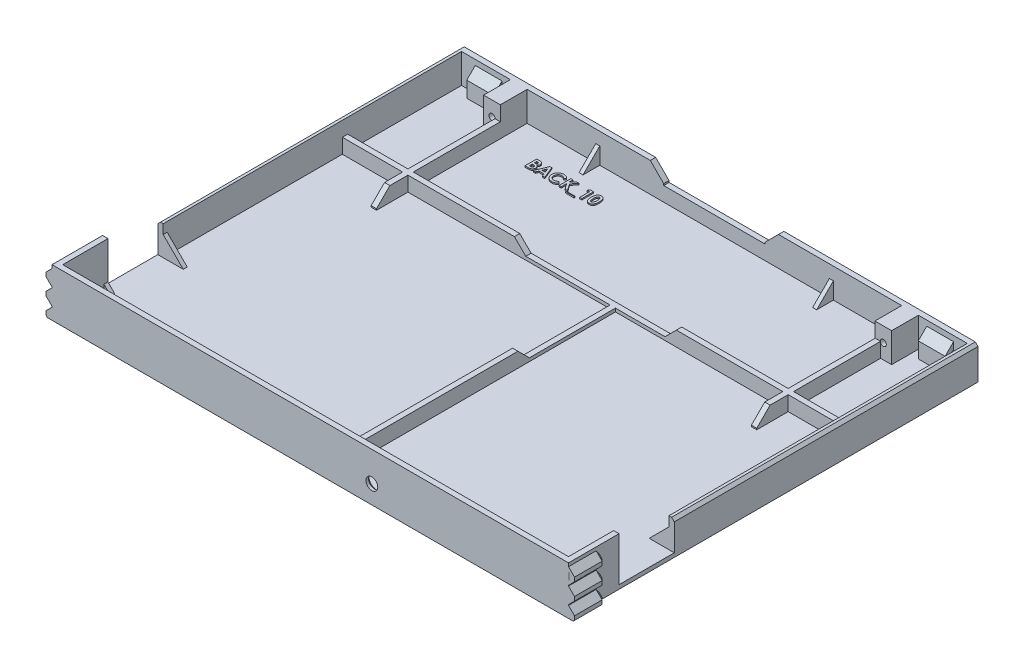
SolidWorks part; units mm, degrees
ref_plane "Front Plane" through (0, 0, 0) normal (0, 0, 1) x (1, 0, 0)
ref_plane "Top Plane" through (0, 0, 0) normal (0, 1, 0) x (1, 0, 0)
ref_plane "Right Plane" through (0, 0, 0) normal (1, 0, 0) x (0, 0, -1)
other "Version"
sketch "Sketch1" plane through (0, 0, 0) normal (0, 1, 0) x (1, 0, 0)
  line L3 (-77.15, -61.17) -> (77.15, -61.17)
  line L5 (-77.15, 61.17) -> (77.15, -61.17) construction
  line L6 (-77.15, -61.17) -> (77.15, 61.17) construction
  line L13 (-77.15, 61.17) -> (-77.15, -61.17)
  line L18 (77.15, 61.17) -> (-77.15, 61.17)
  line L20 (77.15, 61.17) -> (77.15, -61.17)
  point P0 (0, 0)
  point P6 (0, 0)
  dimension "D3" = 154.3
  dimension "D1" = 154.3
  dimension "D2" = 122.34
extrude "flat_on_wall" add sketch "Sketch1" along normal blind 1.2
sketch "Sketch3" plane through (0, 0, 0) normal (0, 1, 0) x (1, 0, 0)
  line L0 (-77.15, -29.57) -> (-77.15, 61.17)
  line L1 (-77.15, 61.17) -> (-77.15, -61.17) construction
  line L2 (-77.15, 61.17) -> (-45.55, 61.17)
  line L3 (77.15, 61.17) -> (-77.15, 61.17) construction
  line L6 (-75.55, 59.57) -> (-75.55, -29.57)
  line L7 (-75.55, -29.57) -> (-77.15, -29.57)
  line L8 (45.55, 61.17) -> (77.15, 61.17)
  line L9 (77.15, 61.17) -> (77.15, -29.57)
  line L10 (77.15, -61.17) -> (77.15, 61.17) construction
  line L11 (77.15, -29.57) -> (75.55, -29.57)
  line L12 (75.55, -29.57) -> (75.55, 59.57)
  line L15 (-77.15, -46.07) -> (-77.15, -61.17)
  line L16 (-77.15, -61.17) -> (77.15, -61.17)
  line L17 (77.15, -61.17) -> (77.15, -46.07)
  line L18 (77.15, -46.07) -> (75.55, -46.07)
  line L19 (75.55, -46.07) -> (75.55, -59.57)
  line L20 (75.55, -59.57) -> (-75.55, -59.57)
  line L21 (-75.55, -59.57) -> (-75.55, -46.07)
  line L22 (-75.55, -46.07) -> (-77.15, -46.07)
  line L23 (-75.55, 59.57) -> (-60.95, 59.57)
  line L24 (-60.95, 59.57) -> (-60.95, 51.57)
  line L25 (-60.95, 51.57) -> (-55.95, 51.57)
  line L26 (-55.95, 51.57) -> (-55.95, 59.57)
  line L27 (-55.95, 59.57) -> (-45.55, 59.57)
  line L28 (75.55, 59.57) -> (60.95, 59.57)
  line L29 (60.95, 59.57) -> (60.95, 51.57)
  line L30 (60.95, 51.57) -> (55.95, 51.57)
  line L31 (55.95, 51.57) -> (55.95, 59.57)
  line L32 (55.95, 59.57) -> (45.55, 59.57)
  line L34 (-45.55, 59.57) -> (45.55, 59.57)
  line L36 (-45.55, 61.17) -> (45.55, 61.17)
  point P25 (-76.35, -46.07)
  dimension "D2" = 1.6
  dimension "D3" = 30
  dimension "D4" = 16.5
  dimension "D5" = 5
  dimension "D6" = 1.6
  dimension "D7" = 30
  dimension "D8" = 16.5
  dimension "D9" = 1.6
  dimension "D10" = 13.5
  dimension "D11" = 1.6
  dimension "D12" = 1.6
  dimension "D13" = 13.5
  dimension "D14" = 14.6
  dimension "D15" = 5
  dimension "D16" = 8
  dimension "D17" = 8
  dimension "D18" = 8
  dimension "D19" = 8
  dimension "D20" = 1.6
  dimension "D21" = 14.6
  dimension "D22" = 1.6
  dimension "D23" = 1.6
extrude "walls" add sketch "Sketch3" along normal blind 10
sketch "Sketch5" plane through (0, 0, 0) normal (1, 0, 0) x (0, 0, -1)
  line L0 (-61.17, 10) -> (-61.17, 0) construction
  line L5 (-61.17, 0) -> (-51.97, 0)
  line L6 (-61.17, 0) -> (-61.17, 2)
  line L7 (-61.17, 2) -> (-51.97, 2)
  line L8 (-51.97, 0) -> (-51.97, 2)
  line L9 (-61.17, 0) -> (61.17, 0) construction
  line L10 (-61.17, 10) -> (-51.97, 10)
  line L11 (-61.17, 5) -> (-51.97, 5)
  line L12 (-61.17, 5) -> (-61.17, 7)
  line L13 (-61.17, 7) -> (-51.97, 7)
  line L14 (-51.97, 5) -> (-51.97, 7)
  line L15 (-61.17, 10) -> (-61.17, 12)
  line L16 (-61.17, 12) -> (-51.97, 12)
  line L17 (-51.97, 10) -> (-51.97, 12)
  line L18 (-61.17, 10) -> (-46.07, 10) construction
  dimension "D1" = 0
  dimension "D2" = 9.2
  dimension "D3" = 2
  dimension "D4" = 9.2
  dimension "D5" = 2
  dimension "D6" = 3
  dimension "D7" = 2
extrude "rails" add sketch "Sketch5" along normal blind 0.75 from surface starting at face at (77.15, 5.3, 18.91)
sketch "Sketch6" plane through (0, 0, 0) normal (1, 0, 0) x (0, 0, -1)
  line L0 (-61.17, 12) -> (-51.97, 12)
  line L1 (-61.17, 2) -> (-51.97, 2)
  line L2 (-61.17, 2) -> (-61.17, 0)
  line L3 (-61.17, 0) -> (-51.97, 0)
  line L4 (-51.97, 2) -> (-51.97, 0)
  line L5 (-61.17, 7) -> (-51.97, 7)
  line L6 (-61.17, 7) -> (-61.17, 5)
  line L7 (-61.17, 5) -> (-51.97, 5)
  line L8 (-51.97, 7) -> (-51.97, 5)
  line L9 (-61.17, 12) -> (-61.17, 10)
  line L10 (-61.17, 10) -> (-51.97, 10)
  line L11 (-51.97, 12) -> (-51.97, 10)
  dimension "D1" = 9.2
  dimension "D2" = 9.2
  dimension "D3" = 2
  dimension "D4" = 2
  dimension "D5" = 2
extrude "rails-left" add sketch "Sketch6" along normal blind 0.1 and the other way blind 1.8 from surface starting at face at (-77.15, 5.3, 18.91)
sketch "Sketch7" plane through (0, 0, 0) normal (0, 1, 0) x (1, 0, 0)
  line L0 (-47.15, 46.17) -> (-47.15, 39.9043) construction
  line L1 (-44.69, 46.17) -> (-44.69, 43.37)
  line L2 (-49.61, 46.17) -> (-49.61, 43.37)
  line L3 (77.15, 61.17) -> (-77.15, 61.17) construction
  line L4 (-77.15, -29.57) -> (-77.15, -46.07) construction
  line L5 (47.15, 46.17) -> (47.15, 39.9043) construction
  line L6 (49.61, 46.17) -> (49.61, 43.37)
  line L7 (44.69, 46.17) -> (44.69, 43.37)
  line L9 (77.15, -29.57) -> (77.15, 61.17) construction
  line L10 (77.15, 61.17) -> (-77.15, 61.17) construction
  line L13 (-77.05, -61.17) -> (77.15, -61.17) construction
  line L14 (-0.45, 8.83) -> (-0.45, 2.5643) construction
  line L15 (2.01, 8.83) -> (2.01, 6.03)
  line L16 (-2.91, 8.83) -> (-2.91, 6.03)
  line L17 (77.15, -46.07) -> (77.15, -29.57) construction
  arc A0 (-44.69, 46.17) -> (-49.61, 46.17) centre (-47.15, 46.17) ccw
  arc A3 (-44.69, 43.37) -> (-49.61, 43.37) centre (-47.15, 39.9043) cw
  arc A4 (49.61, 46.17) -> (44.69, 46.17) centre (47.15, 46.17) ccw
  arc A5 (49.61, 43.37) -> (44.69, 43.37) centre (47.15, 39.9043) cw
  arc A8 (2.01, 8.83) -> (-2.91, 8.83) centre (-0.45, 8.83) ccw
  arc A9 (2.01, 6.03) -> (-2.91, 6.03) centre (-0.45, 2.5643) cw
  point P2 (-47.9176, 44.8712)
  point P13 (43.1175, 41.9506)
  dimension "D1" = 15
  dimension "D5" = 2.46
  dimension "D9" = 4.25
  dimension "D2" = 30
  dimension "D3" = 15
  dimension "D4" = 30
  dimension "D6" = 6.2657
  dimension "D7" = 77.6
  dimension "D8" = 70
extrude "Cut-Extrude7" [suppressed] cut sketch "Sketch7" against normal through all from surface
sketch "Sketch8" plane through (0, 0, -51.57) normal (0, 0, 1) x (1, 0, 0)
  line L0 (-60.95, 10) -> (-60.95, 1.2) construction
  line L1 (-60.95, 10) -> (-55.95, 10) construction
  line L2 (55.95, 10) -> (55.95, 1.2) construction
  line L3 (55.95, 10) -> (60.95, 10) construction
  line L4 (-75.55, 10) -> (-60.95, 10) construction
  line L5 (-63.45, 3) -> (-71.45, 3)
  line L6 (-63.45, 3) -> (-63.45, 8)
  line L7 (-63.45, 8) -> (-71.45, 8)
  line L8 (-71.45, 3) -> (-71.45, 8)
  line L9 (-60.95, 1.2) -> (-75.55, 1.2) construction
  line L10 (-75.55, 10) -> (-75.55, 1.2) construction
  line L11 (-75.55, 10) -> (-75.55, 1.2)
  line L12 (-75.55, 1.2) -> (0, 1.2)
  line L13 (0, 1.2) -> (0, 10)
  line L14 (71.45, 3) -> (71.45, 8)
  line L15 (63.45, 8) -> (71.45, 8)
  line L16 (63.45, 3) -> (63.45, 8)
  line L17 (63.45, 3) -> (71.45, 3)
  circle A0 centre (-58.45, 5.6) radius 0.9
  circle A1 centre (58.45, 5.6) radius 0.9
  circle A2 centre (58.45, 5.6) radius 0.9 construction
  dimension "D1" = 2.5
  dimension "D3" = 2.5
  dimension "D2" = 4.4
  dimension "D4" = 4.4
  dimension "D5" = 5
  dimension "D6" = 8
  dimension "D7" = 5
  dimension "D8" = 2
  dimension "D9" = 1.8
  dimension "D10" = 75.55
extrude "Cut-Extrude8" cut sketch "Sketch8" against normal blind 10 contours A0 | A1 | L8 L5 L6 L7 | L16 L17 L14 L15
sketch "Sketch9" plane through (0, 1.2, 0) normal (0, 1, 0) x (1, 0, 0)
  line L0 (-75.55, 59.57) -> (-75.55, -29.57) construction
  line L7 (0.05, -59.57) -> (0.05, 37.2031)
  line L8 (-75.55, -59.57) -> (75.55, -59.57) construction
  line L9 (75.55, -59.57) -> (75.55, -46.07) construction
  line L12 (-55.95, 51.57) -> (-57.55, 51.57)
  line L13 (-55.95, 51.57) -> (-55.95, 25.5612)
  line L14 (-55.95, 14.57) -> (-57.55, 14.57)
  line L15 (-57.55, 51.57) -> (-57.55, 25.5612)
  line L16 (-75.55, 25.5612) -> (-57.55, 25.5612)
  line L17 (-75.55, 25.5612) -> (-75.55, 23.9612)
  line L18 (-75.55, 23.9612) -> (-57.55, 23.9612)
  line L19 (-20.55, 25.5612) -> (-20.55, 23.9612)
  line L20 (-55.95, 25.5612) -> (-20.55, 25.5612)
  line L21 (-55.95, 23.9612) -> (-20.55, 23.9612)
  line L22 (-55.95, 23.9612) -> (-55.95, 14.57)
  line L23 (-57.55, 23.9612) -> (-57.55, 14.57)
  line L24 (57.65, 23.9612) -> (57.65, 14.57)
  line L25 (56.05, 23.9612) -> (56.05, 14.57)
  line L26 (56.05, 23.9612) -> (20.65, 23.9612)
  line L27 (56.05, 25.5612) -> (20.65, 25.5612)
  line L28 (20.65, 25.5612) -> (20.65, 23.9612)
  line L29 (75.65, 23.9612) -> (57.65, 23.9612)
  line L30 (75.65, 25.5612) -> (75.65, 23.9612)
  line L31 (75.65, 25.5612) -> (57.65, 25.5612)
  line L32 (57.65, 51.57) -> (57.65, 25.5612)
  line L33 (56.05, 14.57) -> (57.65, 14.57)
  line L34 (56.05, 51.57) -> (56.05, 25.5612)
  line L35 (56.05, 51.57) -> (57.65, 51.57)
  line L36 (-75.55, -59.57) -> (75.55, -59.57) construction
  line L37 (4.45, -59.57) -> (6.05, -59.57)
  line L38 (4.45, -59.57) -> (4.45, -1.57)
  line L39 (4.45, -1.57) -> (6.05, -1.57)
  line L40 (6.05, -59.57) -> (6.05, -1.57)
  line L41 (-75.55, 59.57) -> (-75.55, -29.57) construction
  line L42 (-55.95, 51.57) -> (-60.95, 51.57) construction
  line L43 (6.05, 23.9612) -> (20.65, 23.9612)
  line L44 (-20.55, 25.5612) -> (20.65, 25.5612)
  line L45 (-20.55, 25.5612) -> (-20.55, 23.9612)
  line L46 (-20.55, 23.9612) -> (4.45, 23.9612)
  line L47 (20.65, 25.5612) -> (20.65, 23.9612)
  line L48 (6.05, -1.57) -> (4.45, -1.57)
  line L49 (6.05, -1.57) -> (6.05, 23.9612)
  line L51 (4.45, -1.57) -> (4.45, 23.9612)
  line L52 (75.65, -47.27) -> (72.65, -47.27)
  line L53 (-75.55, -29.57) -> (-69.55, -29.57)
  line L54 (-75.55, -29.57) -> (-75.55, -28.37)
  line L55 (-75.55, -28.37) -> (-69.55, -28.37)
  line L56 (-69.55, -29.57) -> (-69.55, -28.37)
  line L57 (-75.55, -46.07) -> (-72.55, -46.07)
  line L58 (-75.55, -46.07) -> (-75.55, -47.27)
  line L59 (-75.55, -47.27) -> (-72.55, -47.27)
  line L60 (-72.55, -46.07) -> (-72.55, -47.27)
  line L61 (72.65, -46.07) -> (72.65, -47.27)
  line L62 (75.65, -46.07) -> (72.65, -46.07)
  line L63 (75.65, -46.07) -> (75.65, -47.27)
  line L64 (75.65, -28.37) -> (69.65, -28.37)
  line L65 (69.65, -29.57) -> (69.65, -28.37)
  line L66 (75.65, -29.57) -> (69.65, -29.57)
  line L67 (75.65, -29.57) -> (75.65, -28.37)
  line L68 (55.95, 59.57) -> (-55.95, 59.57) construction
  line L69 (-35.45, 59.57) -> (-34.25, 59.57)
  line L70 (-35.45, 59.57) -> (-35.45, 54.57)
  line L71 (-35.45, 54.57) -> (-34.25, 54.57)
  line L72 (-34.25, 59.57) -> (-34.25, 54.57)
  line L73 (-55.95, 59.57) -> (-55.95, 51.57) construction
  line L74 (35.55, 54.57) -> (34.35, 54.57)
  line L75 (34.35, 59.57) -> (34.35, 54.57)
  line L76 (35.55, 59.57) -> (34.35, 59.57)
  line L77 (35.55, 59.57) -> (35.55, 54.57)
  point P39 (5.25, -1.57)
  point P42 (-56.75, 14.57)
  point P57 (-69.55, -28.97)
  line M17 (-75.55, -59.57) -> (75.55, -59.57)
  line M22 (75.55, -29.57) -> (75.55, 59.57)
  line M25 (60.95, 51.57) -> (55.95, 51.57)
  line M29 (-55.95, 51.57) -> (-60.95, 51.57)
  line M32 (-75.55, 59.57) -> (-75.55, -29.57)
  dimension "D1" = 1.6
  dimension "D2" = 6
  dimension "D3" = 75.5
  dimension "D4" = 1.6
  dimension "D5" = 1.6
  dimension "D6" = 58
  dimension "D7" = 55
  dimension "D8" = 37
  dimension "D9" = 1.2
  dimension "D10" = 1.2
  dimension "D11" = 3
  dimension "D12" = 6
  dimension "D13" = 1.2
  dimension "D14" = 5
  dimension "D15" = 20.5
extrude "Boss-Extrude8" add sketch "Sketch9" along normal blind 4.4 contours L18 L23 L14 L22 L21 L19 L20 L13 L15 L16 M29 M32 | L40 L39 L38 M17 | L34 L27 L28 L26 L25 L33 L24 L29 L31 L32 M25 M22 region at (5.25, 1.2, 30.57) region at (-38.25, 1.2, -24.624) region at (38.35, 1.2, -24.8991)
sketch "Sketch16" plane through (0, 10, 0) normal (0, 1, 0) x (1, 0, 0)
  line L2 (77.15, -61.17) -> (77.15, -46.07)
  line L3 (77.15, -46.07) -> (75.55, -46.07)
  line L4 (75.55, -46.07) -> (75.55, -59.57)
  line L5 (75.55, -59.57) -> (-75.55, -59.57)
  line L6 (-75.55, -59.57) -> (-75.55, -46.07)
  line L7 (-75.55, -46.07) -> (-77.15, -46.07)
  line L8 (-77.15, -46.07) -> (-77.15, -61.17)
  line L11 (-77.15, -61.17) -> (77.15, -61.17)
extrude "Boss-Extrude9" add sketch "Sketch16" along normal blind 4.4
chamfer "Rail Chamfers" distance 0.8 angle 45 10 edges at (77.525, 7, 51.97) (77.525, 5, 51.97) (77.525, 2, 51.97) (77.525, 0, 51.97) (-78.05, 12, 51.97) (-78.05, 10, 51.97) (-78.05, 7, 51.97) (-78.05, 5, 51.97) (-78.05, 2, 51.97) (-78.05, 0, 51.97)
chamfer "Rail Chamfers 2" distance 0.8 angle 45 2 edges at (77.525, 12, 51.97) (77.525, 10, 51.97)
chamfer "Wall Chamfers" distance 0.8 angle 45 2 edges at (77.15, 10, -15.8) (-77.15, 10, -15.8)
sketch "Sketch18" plane through (0, 0, -61.17) normal (0, 0, -1) x (-1, 0, 0)
  line L0 (-76.35, 10) -> (76.35, 10) construction
  line L1 (-15.15, 10) -> (15.15, 10)
  line L2 (-15.15, 10) -> (-15.15, 5.5)
  line L3 (-15.15, 5.5) -> (15.15, 5.5)
  line L4 (15.15, 10) -> (15.15, 5.5)
  line L5 (-77.15, 9.2) -> (-77.15, 0) construction
  line L6 (77.15, 9.2) -> (77.15, 0) construction
  dimension "D1" = 62
  dimension "D2" = 62
  dimension "D3" = 4.5
extrude "Ribbon Hole" cut sketch "Sketch18" against normal blind 10
chamfer "Chamfer1" distance 0.4 angle 45 30 edges at (-78.95, 10.4, 52.37) (-78.95, 11, 51.97) (-78.95, 11.6, 52.37) (-78.95, 12, 56.97) (-78.95, 11, 61.17) (-78.95, 10, 56.97) (-78.95, 5.4, 52.37) (-78.95, 6, 51.97) (-78.95, 6.6, 52.37) (-78.95, 7, 56.97) (-78.95, 6, 61.17) (-78.95, 5, 56.97) (-78.95, 0.4, 52.37) (-78.95, 1, 51.97) (-78.95, 1.6, 52.37) (-78.95, 2, 56.97) (-78.95, 1, 61.17) (-78.95, 0, 56.97) (77.9, 1.6, 52.37) (77.9, 1, 51.97) (77.9, 0.4, 52.37) (77.9, 0, 56.97) (77.9, 2, 56.97) (77.9, 1, 61.17) (77.9, 6, 61.17) (77.9, 5, 56.97) (77.9, 5.4, 52.37) (77.9, 6, 51.97) (77.9, 6.6, 52.37) (77.9, 7, 56.97)
chamfer "Chamfer2" distance 0.4 angle 45 6 edges at (77.9, 11, 51.97) (77.9, 10.4, 52.37) (77.9, 10, 56.97) (77.9, 11, 61.17) (77.9, 11.6, 52.37) (77.9, 12, 56.97)
sketch "Sketch19" plane through (0, 0, 61.17) normal (0, 0, 1) x (1, 0, 0)
  line L0 (-78.55, 0) -> (77.5, 0) construction
  line L2 (15.9, 5.5) -> (15.9, 14.5133) construction
  line L3 (20.9, 5.5) -> (20.9, 14.5133) construction
  line L4 (15.9, 14.5133) -> (20.9, 14.5133) construction
  line L6 (18.4, 3) -> (15.9, 5.5)
  line L7 (18.4, 3) -> (20.9, 5.5)
  line L8 (20.9, 5.5) -> (18.4, 8)
  line L9 (18.4, 8) -> (15.9, 5.5)
  arc A0 (15.9, 5.5) -> (20.9, 5.5) centre (18.4, 5.5) ccw construction
  circle A1 centre (18.4, 5.5) radius 1.7678
  line M17 (-78.55, 5) -> (-77.15, 5)
  dimension "D1" = 5.5
  dimension "D3" = 5
  dimension "D2" = 18.4
extrude "Cut-Extrude9" cut sketch "Sketch19" against normal blind 10 contours A1 M17 region at (18.4, 5.5, 61.17)
sketch "Sketch20" plane through (0, 0, 61.17) normal (0, 0, 1) x (1, 0, 0)
  line L0 (-78.95, 11.6) -> (-78.95, 10.4)
  line L1 (-78.95, 10.4) -> (-77.05, 8.5)
  line L2 (-78.95, 11.6) -> (-77.15, 13.4)
  line L4 (-77.15, 14.4) -> (-77.15, 12) construction
  line L7 (-78.95, 1.6) -> (-77.05, 3.5)
  line L9 (-78.95, 5.4) -> (-77.05, 3.5)
  line L10 (-78.95, 6.6) -> (-78.95, 5.4)
  line L11 (-78.95, 6.6) -> (-77.05, 8.5)
  line L12 (-78.95, 1.6) -> (-78.95, 0.4)
  line L13 (-78.95, 0.4) -> (-78.55, 0)
  line L15 (-78.55, 10) -> (-78.95, 10.4) construction
  line L16 (-77.15, 13.4) -> (-76.932, 13.4)
  line L19 (-78.55, 0) -> (-76.932, 0)
  line L22 (-78.55, 7) -> (-78.95, 6.6) construction
  line L23 (-76.932, 13.4) -> (-76.932, 0)
extrude "Boss-Extrude11" add sketch "Sketch20" against normal blind 9.25
sketch "Sketch21" plane through (-71.45, 0, 0) normal (1, 0, 0) x (0, 0, -1)
  line L0 (61.17, 8) -> (58.4281, 5.2665)
  line L1 (58.4281, 5.2665) -> (58.4281, 1.2)
  line L2 (59.57, 1.2) -> (25.5612, 1.2) construction
  line L3 (57.0393, 1.2) -> (57.0393, 5.8819)
  line L4 (57.0393, 5.8819) -> (61.17, 10)
  line L6 (58.4281, 1.2) -> (57.0393, 1.2)
  line L7 (61.17, 10) -> (61.17, 8)
extrude "Boss-Extrude17" add sketch "Sketch21" along normal blind 8
mirror "Mirror2" about plane through (0, 0, 0) normal (1, 0, 0) of "Boss-Extrude17", "Boss-Extrude11"
chamfer "Chamfer3" distance 1 angle 45 18 edges at (-78.75, 0.2, 51.92) (-78.95, 1, 51.92) (-78.05, 2.5, 51.92) (-78.05, 4.5, 51.92) (-78.95, 6, 51.92) (-78.05, 7.5, 51.92) (-78.05, 9.5, 51.92) (-78.95, 11, 51.92) (-78.05, 12.5, 51.92) (78.75, 0.2, 51.92) (78.95, 1, 51.92) (78.05, 2.5, 51.92) (78.05, 4.5, 51.92) (78.95, 6, 51.92) (78.05, 7.5, 51.92) (78.05, 9.5, 51.92) (78.95, 11, 51.92) (78.05, 12.5, 51.92)
chamfer "Chamfer4" distance 4 angle 45 2 edges at (15.15, 10, -60.37) (-15.15, 10, -60.37)
sketch "Sketch22" plane through (0, 1.2, 0) normal (0, 1, 0) x (1, 0, 0)
  text T0 "<b>BACK_10</b>"
extrude "Version Number" add sketch "Sketch22" along normal blind 0.4
extrude "Boss-Extrude19" add sketch "Sketch9<11>" along normal blind 1 contours L51 L39 L49 L43 L28 L44 L7 L46 | L19 L46 L7 L44 region at (-10.25, 1.2, -24.7612) region at (0.3907, 1.2, -24.7612)
sketch "Sketch9<11>" plane through (0, 1.2, 0) normal (0, 1, 0) x (1, 0, 0) same geometry as "Sketch9"
chamfer "Chamfer6" distance 3.6 angle 45 3 edges at (5.25, 5.6, 1.57) (20.65, 5.6, -24.7612) (-20.55, 5.6, -24.7612)
extrude "Boss-Extrude20" add sketch "Sketch9<12>" along normal blind 6 contours L55 L56 L53 L54 | L66 L65 L64 L67
sketch "Sketch9<12>" plane through (0, 1.2, 0) normal (0, 1, 0) x (1, 0, 0) same geometry as "Sketch9"
extrude "Boss-Extrude21" add sketch "Sketch9<13>" along normal blind 6 contours L57 L60 L59 L58 | L52 L61 L62 L63
sketch "Sketch9<13>" plane through (0, 1.2, 0) normal (0, 1, 0) x (1, 0, 0) same geometry as "Sketch9"
chamfer "Chamfer7" distance 7 angle 45 2 edges at (72.65, 7.2, 46.67) (-72.55, 7.2, 46.67)
chamfer "Chamfer8" distance 6 angle 45 2 edges at (69.65, 7.2, 28.97) (-69.55, 7.2, 28.97)
extrude "Boss-Extrude22" add sketch "Sketch9<14>" along normal blind 5 contours L70 L71 L72 L69 | L75 L74 L77 L76
sketch "Sketch9<14>" plane through (0, 1.2, 0) normal (0, 1, 0) x (1, 0, 0) same geometry as "Sketch9"
chamfer "Chamfer9" distance 5 angle 45 2 edges at (-34.85, 6.2, -54.57) (34.95, 6.2, -54.57)
chamfer "Chamfer10" distance 0.8 angle 45 1 edges at (20.1678, 5.5, 59.57)
chamfer "Chamfer11" distance 4 angle 45 2 edges at (56.85, 5.6, -14.57) (-56.75, 5.6, -14.57)
